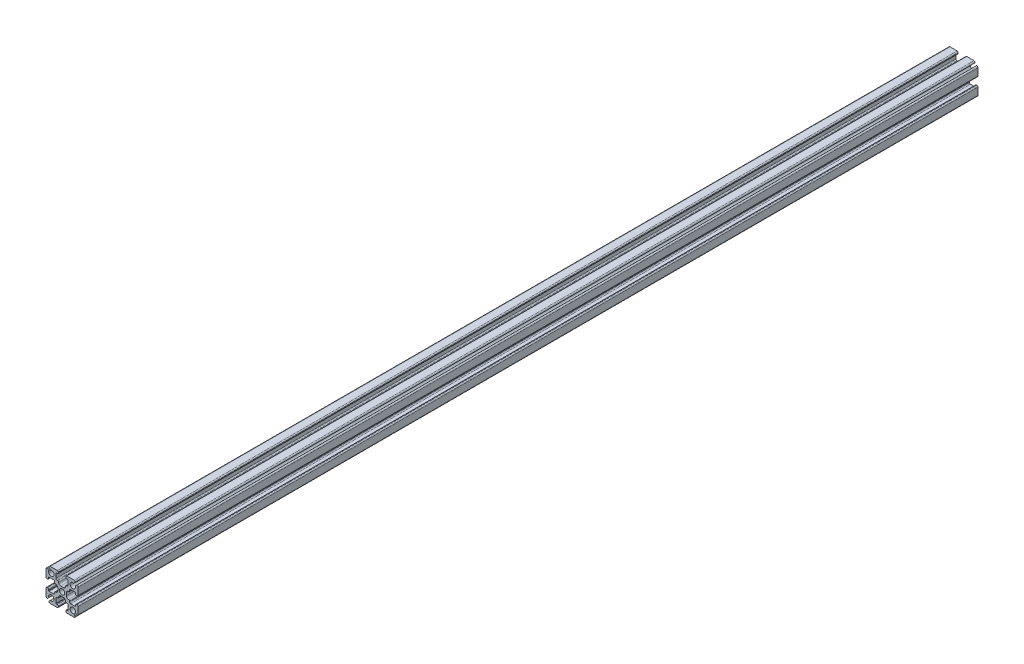
SolidWorks part; units mm, degrees
ref_plane "Front Plane" through (0, 0, 0) normal (0, 0, 1) x (1, 0, 0)
ref_plane "Top Plane" through (0, 0, 0) normal (0, 1, 0) x (1, 0, 0)
ref_plane "Right Plane" through (0, 0, 0) normal (1, 0, 0) x (0, 0, -1)
ref_plane "Plane1" through (0, 0, 420) normal (0, 0, 1) x (1, 0, 0)
sketch "Sketch1" plane through (0, 0, 420) normal (0, 0, 1) x (1, 0, 0)
  line L0 (-5.9393, 6.6464) -> (-5.4565, 6.1636)
  line L1 (-6.1636, 5.4565) -> (-6.6464, 5.9393)
  line L2 (-7.5, 5.5858) -> (-7.5, 2.25)
  line L3 (-7, 1.75) -> (-6.8, 1.75)
  line L4 (-6.3, 2.25) -> (-6.3, 2.65)
  line L5 (-6.1, 2.85) -> (-4, 2.85)
  line L6 (-3.5, 2.35) -> (-3.5, 2.1)
  line L7 (-2, 0.6) -> (-2, -0.6)
  line L8 (-3.5, -2.1) -> (-3.5, -2.35)
  line L9 (-4, -2.85) -> (-6.1, -2.85)
  line L10 (-6.3, -2.65) -> (-6.3, -2.25)
  line L11 (-6.8, -1.75) -> (-7, -1.75)
  line L12 (-7.5, -2.25) -> (-7.5, -5.5858)
  line L13 (-6.6464, -5.9393) -> (-6.1636, -5.4565)
  line L14 (-5.4565, -6.1636) -> (-5.9393, -6.6464)
  line L15 (-5.5858, -7.5) -> (-2.25, -7.5)
  line L16 (-1.75, -7) -> (-1.75, -6.8)
  line L17 (-2.25, -6.3) -> (-2.65, -6.3)
  line L18 (-2.85, -6.1) -> (-2.85, -4)
  line L19 (-2.35, -3.5) -> (-2.1, -3.5)
  line L20 (-0.6, -2) -> (0.6, -2)
  line L21 (2.1, -3.5) -> (2.35, -3.5)
  line L22 (2.85, -4) -> (2.85, -6.1)
  line L23 (2.65, -6.3) -> (2.25, -6.3)
  line L24 (1.75, -6.8) -> (1.75, -7)
  line L25 (2.25, -7.5) -> (5.5858, -7.5)
  line L26 (5.9393, -6.6464) -> (5.4565, -6.1636)
  line L27 (6.1636, -5.4565) -> (6.6464, -5.9393)
  line L28 (7.5, -5.5858) -> (7.5, -2.25)
  line L29 (7, -1.75) -> (6.8, -1.75)
  line L30 (6.3, -2.25) -> (6.3, -2.65)
  line L31 (6.1, -2.85) -> (4, -2.85)
  line L32 (3.5, -2.35) -> (3.5, -2.1)
  line L33 (2, -0.6) -> (2, 0.6)
  line L34 (3.5, 2.1) -> (3.5, 2.35)
  line L35 (4, 2.85) -> (6.1, 2.85)
  line L36 (6.3, 2.65) -> (6.3, 2.25)
  line L37 (6.8, 1.75) -> (7, 1.75)
  line L38 (7.5, 2.25) -> (7.5, 5.5858)
  line L39 (6.6464, 5.9393) -> (6.1636, 5.4565)
  line L40 (5.4565, 6.1636) -> (5.9393, 6.6464)
  line L41 (5.5858, 7.5) -> (2.25, 7.5)
  line L42 (1.75, 7) -> (1.75, 6.8)
  line L43 (2.25, 6.3) -> (2.65, 6.3)
  line L44 (2.85, 6.1) -> (2.85, 4)
  line L45 (2.35, 3.5) -> (2.1, 3.5)
  line L46 (0.6, 2) -> (-0.6, 2)
  line L47 (-2.1, 3.5) -> (-2.35, 3.5)
  line L48 (-2.85, 4) -> (-2.85, 6.1)
  line L49 (-2.65, 6.3) -> (-2.25, 6.3)
  line L50 (-1.75, 6.8) -> (-1.75, 7)
  line L51 (-2.25, 7.5) -> (-5.5858, 7.5)
  circle A0 centre (0, 0) radius 1.25
  arc A1 (-5.5858, 7.5) -> (-5.9393, 6.6464) centre (-5.5858, 7) ccw
  arc A2 (-5.4565, 6.1636) -> (-6.1636, 5.4565) centre (-5, 5) cw
  arc A3 (-6.6464, 5.9393) -> (-7.5, 5.5858) centre (-7, 5.5858) ccw
  arc A4 (-7.5, 2.25) -> (-7, 1.75) centre (-7, 2.25) ccw
  arc A5 (-6.8, 1.75) -> (-6.3, 2.25) centre (-6.8, 2.25) ccw
  arc A6 (-6.3, 2.65) -> (-6.1, 2.85) centre (-6.1, 2.65) cw
  arc A7 (-4, 2.85) -> (-3.5, 2.35) centre (-4, 2.35) cw
  arc A8 (-3.5, 2.1) -> (-3, 1.6) centre (-3, 2.1) ccw
  arc A9 (-3, 1.6) -> (-2, 0.6) centre (-3, 0.6) cw
  arc A10 (-2, -0.6) -> (-3, -1.6) centre (-3, -0.6) cw
  arc A11 (-3, -1.6) -> (-3.5, -2.1) centre (-3, -2.1) ccw
  arc A12 (-3.5, -2.35) -> (-4, -2.85) centre (-4, -2.35) cw
  arc A13 (-6.1, -2.85) -> (-6.3, -2.65) centre (-6.1, -2.65) cw
  arc A14 (-6.3, -2.25) -> (-6.8, -1.75) centre (-6.8, -2.25) ccw
  arc A15 (-7, -1.75) -> (-7.5, -2.25) centre (-7, -2.25) ccw
  arc A16 (-7.5, -5.5858) -> (-6.6464, -5.9393) centre (-7, -5.5858) ccw
  arc A17 (-6.1636, -5.4565) -> (-5.4565, -6.1636) centre (-5, -5) cw
  arc A18 (-5.9393, -6.6464) -> (-5.5858, -7.5) centre (-5.5858, -7) ccw
  arc A19 (-2.25, -7.5) -> (-1.75, -7) centre (-2.25, -7) ccw
  arc A20 (-1.75, -6.8) -> (-2.25, -6.3) centre (-2.25, -6.8) ccw
  arc A21 (-2.65, -6.3) -> (-2.85, -6.1) centre (-2.65, -6.1) cw
  arc A22 (-2.85, -4) -> (-2.35, -3.5) centre (-2.35, -4) cw
  arc A23 (-2.1, -3.5) -> (-1.6, -3) centre (-2.1, -3) ccw
  arc A24 (-1.6, -3) -> (-0.6, -2) centre (-0.6, -3) cw
  arc A25 (0.6, -2) -> (1.6, -3) centre (0.6, -3) cw
  arc A26 (1.6, -3) -> (2.1, -3.5) centre (2.1, -3) ccw
  arc A27 (2.35, -3.5) -> (2.85, -4) centre (2.35, -4) cw
  arc A28 (2.85, -6.1) -> (2.65, -6.3) centre (2.65, -6.1) cw
  arc A29 (2.25, -6.3) -> (1.75, -6.8) centre (2.25, -6.8) ccw
  arc A30 (1.75, -7) -> (2.25, -7.5) centre (2.25, -7) ccw
  arc A31 (5.5858, -7.5) -> (5.9393, -6.6464) centre (5.5858, -7) ccw
  arc A32 (5.4565, -6.1636) -> (6.1636, -5.4565) centre (5, -5) cw
  arc A33 (6.6464, -5.9393) -> (7.5, -5.5858) centre (7, -5.5858) ccw
  arc A34 (7.5, -2.25) -> (7, -1.75) centre (7, -2.25) ccw
  arc A35 (6.8, -1.75) -> (6.3, -2.25) centre (6.8, -2.25) ccw
  arc A36 (6.3, -2.65) -> (6.1, -2.85) centre (6.1, -2.65) cw
  arc A37 (4, -2.85) -> (3.5, -2.35) centre (4, -2.35) cw
  arc A38 (3.5, -2.1) -> (3, -1.6) centre (3, -2.1) ccw
  arc A39 (3, -1.6) -> (2, -0.6) centre (3, -0.6) cw
  arc A40 (2, 0.6) -> (3, 1.6) centre (3, 0.6) cw
  arc A41 (3, 1.6) -> (3.5, 2.1) centre (3, 2.1) ccw
  arc A42 (3.5, 2.35) -> (4, 2.85) centre (4, 2.35) cw
  arc A43 (6.1, 2.85) -> (6.3, 2.65) centre (6.1, 2.65) cw
  arc A44 (6.3, 2.25) -> (6.8, 1.75) centre (6.8, 2.25) ccw
  arc A45 (7, 1.75) -> (7.5, 2.25) centre (7, 2.25) ccw
  arc A46 (7.5, 5.5858) -> (6.6464, 5.9393) centre (7, 5.5858) ccw
  arc A47 (6.1636, 5.4565) -> (5.4565, 6.1636) centre (5, 5) cw
  arc A48 (5.9393, 6.6464) -> (5.5858, 7.5) centre (5.5858, 7) ccw
  arc A49 (2.25, 7.5) -> (1.75, 7) centre (2.25, 7) ccw
  arc A50 (1.75, 6.8) -> (2.25, 6.3) centre (2.25, 6.8) ccw
  arc A51 (2.65, 6.3) -> (2.85, 6.1) centre (2.65, 6.1) cw
  arc A52 (2.85, 4) -> (2.35, 3.5) centre (2.35, 4) cw
  arc A53 (2.1, 3.5) -> (1.6, 3) centre (2.1, 3) ccw
  arc A54 (1.6, 3) -> (0.6, 2) centre (0.6, 3) cw
  arc A55 (-0.6, 2) -> (-1.6, 3) centre (-0.6, 3) cw
  arc A56 (-1.6, 3) -> (-2.1, 3.5) centre (-2.1, 3) ccw
  arc A57 (-2.35, 3.5) -> (-2.85, 4) centre (-2.35, 4) cw
  arc A58 (-2.85, 6.1) -> (-2.65, 6.3) centre (-2.65, 6.1) cw
  arc A59 (-2.25, 6.3) -> (-1.75, 6.8) centre (-2.25, 6.8) ccw
  arc A60 (-1.75, 7) -> (-2.25, 7.5) centre (-2.25, 7) ccw
extrude "Boss-Extrude1" add sketch "Sketch1" against normal blind 420
